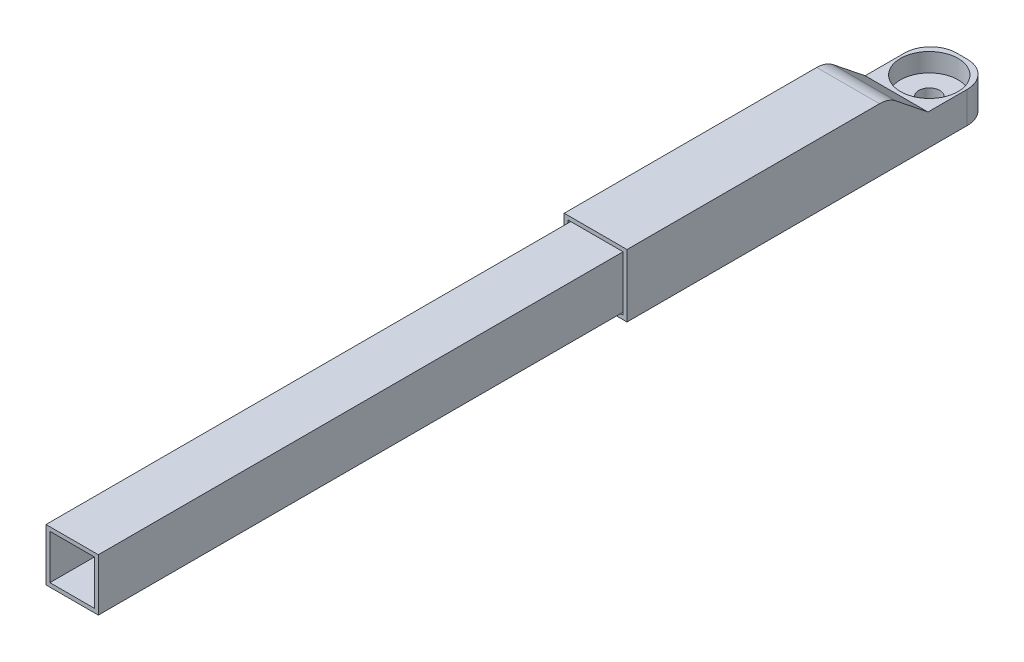
SolidWorks part; units mm, degrees
note: The reader was unsure of these and kept them because the rebuilt part matched: shared geometry of "Sketch9<4>".
ref_plane "Front Plane" through (0, 0, 0) normal (0, 0, 1) x (1, 0, 0)
ref_plane "Top Plane" through (0, 0, 0) normal (0, 1, 0) x (1, 0, 0)
ref_plane "Right Plane" through (0, 0, 0) normal (1, 0, 0) x (0, 0, -1)
sketch "Sketch1" plane through (0, 0, 0) normal (0, 0, 1) x (1, 0, 0)
  line L0 (-8.5, 8.5) -> (8.5, 8.5)
  line L1 (-10, -10) -> (10, -10)
  line L2 (-10, -10) -> (-10, 10)
  line L3 (-10, 10) -> (10, 10)
  line L4 (10, -10) -> (10, 10)
  line L5 (-10, -10) -> (10, 10) construction
  line L6 (-10, 10) -> (10, -10) construction
  line L7 (8.5, -8.5) -> (8.5, 8.5)
  line L8 (-8.5, -8.5) -> (8.5, -8.5)
  line L9 (-8.5, -8.5) -> (-8.5, 8.5)
  point P0 (0, 0)
  dimension "D1" = 20
  dimension "D2" = 20
  dimension "D3" = 1.5
extrude "Boss-Extrude1" add sketch "Sketch1" along normal blind 300
sketch "Sketch2" plane through (0, 0, 0) normal (0, 0, -1) x (-1, 0, 0)
  line L1 (-8, -8) -> (8, -8)
  line L2 (-8, -8) -> (-8, 8)
  line L3 (-8, 8) -> (8, 8)
  line L4 (8, -8) -> (8, 8)
  line L5 (-8, -8) -> (8, 8) construction
  line L6 (-8, 8) -> (8, -8) construction
  line L7 (-8, -0.25) -> (-8.5, -0.25)
  line L9 (-8, 0.25) -> (-8.5, 0.25)
  line L10 (-8.5, -0.25) -> (-8.5, 0.25)
  line L11 (-8, 0) -> (-8.5, 0.25) construction
  line L12 (-8, 0) -> (-8.5, -0.25) construction
  line L13 (0.25, 8) -> (0.25, 8.5)
  line L14 (-0.25, 8.5) -> (0.25, 8.5)
  line L15 (-0.25, 8) -> (-0.25, 8.5)
  line L17 (8, -0.25) -> (8.5, -0.25)
  line L18 (8.5, 0.25) -> (8.5, -0.25)
  line L19 (8, 0.25) -> (8.5, 0.25)
  line L20 (-12, 12) -> (12, 12)
  line L21 (-10.5, -10.5) -> (10.5, -10.5)
  line L22 (-10.5, -10.5) -> (-10.5, 10.5)
  line L23 (-10.5, 10.5) -> (10.5, 10.5)
  line L24 (10.5, -10.5) -> (10.5, 10.5)
  line L25 (-10.5, -10.5) -> (10.5, 10.5) construction
  line L26 (-10.5, 10.5) -> (10.5, -10.5) construction
  line L27 (12, -12) -> (12, 12)
  line L28 (-12, -12) -> (12, -12)
  line L29 (-12, -12) -> (-12, 12)
  point P1 (0, 0)
  point P6 (0, 8)
  point P7 (-8, 0)
  point P18 (8, 0)
  point P21 (0, 0)
  point P23 (0, 0)
  line M26 (-8.5, 8.5) -> (8.5, 8.5)
  line M27 (8.5, 8.5) -> (8.5, -8.5)
  line M29 (-8.5, -8.5) -> (-8.5, 8.5)
  dimension "D1" = 16
  dimension "D2" = 16
  dimension "D3" = 0.25
  dimension "D4" = 0.5
  dimension "D6" = 8
  dimension "D7" = 8
  dimension "D8" = 8
  dimension "D9" = 0.5
  dimension "D10" = 21
  dimension "D11" = 21
  dimension "D12" = 1.5
  dimension "D5" = 3
extrude "Boss-Extrude2" add sketch "Sketch2" against normal blind 100 separate body contours L1 L4 L3 L2 | L15 L3 L13 M26 | L19 L4 L17 M27 | L2 L9 L7 M29 | L29 L28 L27 L20 L24 L21 L22 L23
sketch "Sketch3" plane through (0, 0, 0) normal (0, 0, -1) x (-1, 0, 0)
  line L0 (-12, -12) -> (-12, 12) construction
  line L1 (-12, -12) -> (12, -12)
  line L2 (-12, -12) -> (-12, 12)
  line L3 (-12, 12) -> (12, 12)
  line L4 (12, -12) -> (12, 12)
  line L5 (-12, -12) -> (12, 12) construction
  line L6 (-12, 12) -> (12, -12) construction
  line L7 (12, -12) -> (12, 12) construction
  point P0 (0, 0)
  dimension "D1" = 24
extrude "Boss-Extrude3" add sketch "Sketch3" against normal blind 5
ref_plane "Plane1" through (0, 0, -50) normal (0, 0, -1) x (-1, 0, 0)
ref_plane "Plane2" through (0, 0, -15) normal (0, 0, -1) x (-1, 0, 0)
sketch "Sketch5" plane through (0, 0, 0) normal (0, 0, -1) x (-1, 0, 0)
  line L1 (-12, -12) -> (12, -12)
  line L2 (-12, -12) -> (-12, 12)
  line L3 (-12, 12) -> (12, 12)
  line L4 (12, -12) -> (12, 12)
  line L5 (-12, -12) -> (12, 12) construction
  line L6 (-12, 12) -> (12, -12) construction
  point P0 (0, 0)
sketch "Sketch6" plane through (0, 0, -15) normal (0, 0, -1) x (-1, 0, 0)
  line L0 (12, -12) -> (12, 12) construction
  line L1 (-12, -12) -> (12, -12)
  line L2 (-12, -12) -> (-12, 0)
  line L3 (-12, 0) -> (12, 0)
  line L4 (12, -12) -> (12, 0)
loft "Loft1" add profiles "Sketch6" section "Sketch6" section face at (0, 0, 0) connector at (12, 0, -15) connector at (12, 12, 0)
sketch "Sketch7" plane through (0, 0, -15) normal (0, 0, -1) x (-1, 0, 0)
  line L1 (-12, -12) -> (12, -12)
  line L2 (-12, -12) -> (-12, 0)
  line L3 (-12, 0) -> (12, 0)
  line L4 (12, -12) -> (12, 0)
extrude "Boss-Extrude5" add sketch "Sketch7" along normal blind 25
fillet "Fillet2" radius 10 2 edges at (-12, -6, -40) (12, -6, -40)
sketch "Sketch9" plane through (0, 0, 0) normal (0, 1, 0) x (1, 0, 0)
  line L0 (0, 40) -> (0, 15)
  line L1 (-2, 40) -> (2, 40) construction
  line L2 (55, 15) -> (-55, 15) construction
  line L3 (-12, 27.5) -> (12, 27.5)
  line L4 (-12, 30) -> (-12, 15) construction
  line L5 (12, 30) -> (12, 15) construction
  circle A0 centre (0, 27.5) radius 4
  circle A1 centre (0, 27.5) radius 11
  dimension "D1" = 8
  dimension "D2" = 22
extrude "Cut-Extrude1" cut sketch "Sketch9" against normal through all contours A0
extrude "Cut-Extrude2" cut sketch "Sketch9<4>" against normal blind 7.1 contours A1
sketch "Sketch9<4>" plane through (0, 0, 0) normal (0, 1, 0) x (1, 0, 0) same geometry as "Sketch9"
fillet "Fillet3" radius 10 1 edges at (0, 12, 0)
